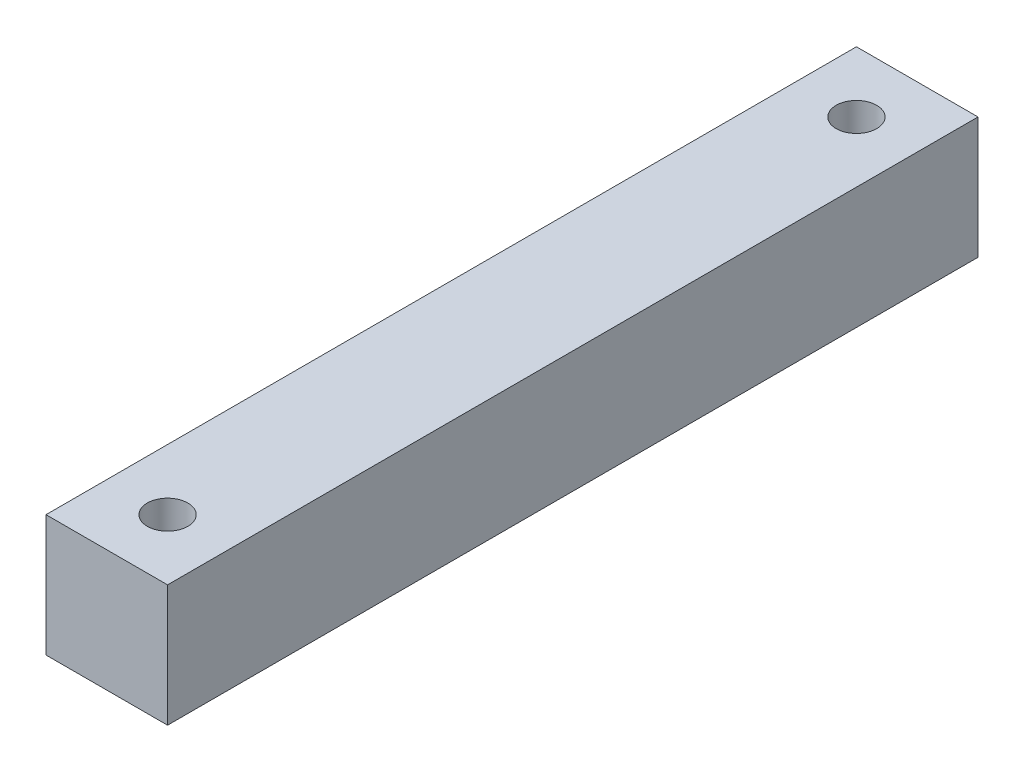
SolidWorks part; units mm, degrees
ref_plane "前视基准面" through (0, 0, 0) normal (0, 0, 1) x (1, 0, 0)
ref_plane "上视基准面" through (0, 0, 0) normal (0, 1, 0) x (1, 0, 0)
ref_plane "右视基准面" through (0, 0, 0) normal (1, 0, 0) x (0, 0, -1)
other "Configuration Table"
sketch "Sketch1" plane through (0, 0, 0) normal (0, 0, 1) x (1, 0, 0)
  line L1 (-30, -30) -> (30, -30)
  line L2 (-30, -30) -> (-30, 30)
  line L3 (-30, 30) -> (30, 30)
  line L4 (30, -30) -> (30, 30)
  line L5 (-30, -30) -> (30, 30) construction
  line L6 (-30, 30) -> (30, -30) construction
  point P0 (0, 0)
extrude "Boss-Extrude1" add sketch "Sketch1" along normal blind 400
sketch "Sketch2" plane through (0, 0, 0) normal (0, 0, 1) x (1, 0, 0)
  circle A0 centre (0, 0) radius 10
extrude "Cut-Extrude1" cut sketch "Sketch2" along normal blind 50
sketch "Sketch3" plane through (0, 0, 0) normal (0, 1, 0) x (1, 0, 0)
  circle A0 centre (0, -30) radius 10
extrude "Cut-Extrude2" cut sketch "Sketch3" along normal blind 60 and the other way blind 60
sketch "Sketch4" plane through (0, 0, 0) normal (0, 1, 0) x (1, 0, 0)
  circle A0 centre (0, -370) radius 10
extrude "Cut-Extrude3" cut sketch "Sketch4" along normal blind 60 and the other way blind 60
sketch3d "3DSketch1"
  line L0 (0, 0, 0) -> (0, 0, 50) construction
ref_axis "axis_1_conn" through (0, 0, 0) along (0, 0, 1)
sketch3d "3DSketch2"
  line L0 (0, -30, 30) -> (0, 30, 30) construction
ref_axis "axis_2_rot" through (0, -30, 30) along (0, 1, 0)
sketch3d "3DSketch3"
  line L0 (0, -30, 370) -> (0, 30, 370) construction
ref_axis "axis_3_rot" through (0, -30, 370) along (0, 1, 0)
ref_plane "arm_bottom_face" through (0, 0, 0) normal (0, 0, 1) x (1, 0, 0)
ref_plane "joint_face_3" through (0, 30, 0) normal (0, 1, 0) x (1, 0, 0)
